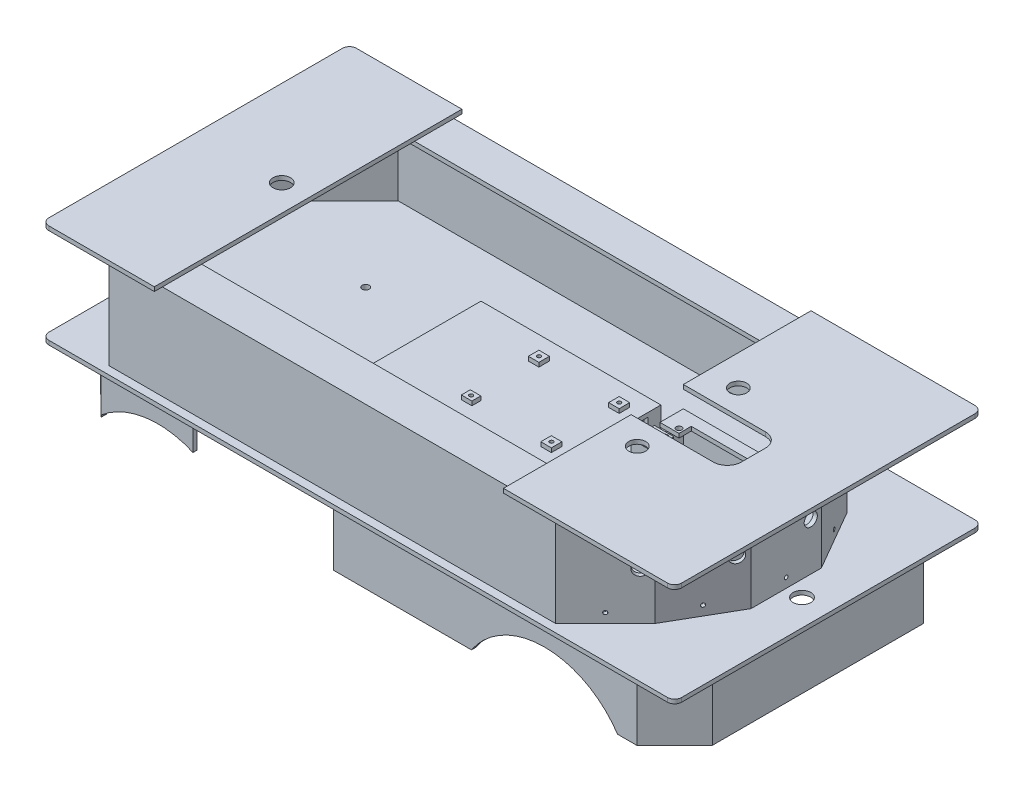
SolidWorks part; units mm, degrees
material "ABS"
ref_plane "Front Plane" through (0, 0, 0) normal (0, 0, 1) x (1, 0, 0)
ref_plane "Top Plane" through (0, 0, 0) normal (0, 1, 0) x (1, 0, 0)
ref_plane "Right Plane" through (0, 0, 0) normal (1, 0, 0) x (0, 0, -1)
sketch "Sketch1" plane through (0, 0, 0) normal (0, 1, 0) x (1, 0, 0)
  line L0 (-303.5027, 0) -> (303.5027, 0) construction
  line L1 (-223.52, -111.125) -> (223.52, -111.125)
  line L2 (-228.6, -106.045) -> (-228.6, 106.045)
  line L3 (-223.52, 111.125) -> (223.52, 111.125)
  line L4 (228.6, -106.045) -> (228.6, 106.045)
  line L5 (-228.6, -111.125) -> (228.6, 111.125) construction
  line L6 (-228.6, 111.125) -> (228.6, -111.125) construction
  line L7 (-303.5027, 36.5125) -> (303.5027, 36.5125) construction
  line L8 (-303.5027, -36.5125) -> (303.5027, -36.5125) construction
  line L9 (127, 111.125) -> (127, -111.125) construction
  line L10 (-142.24, 111.125) -> (-142.24, -111.125) construction
  arc A0 (223.52, 111.125) -> (228.6, 106.045) centre (223.52, 106.045) cw
  arc A1 (223.52, -111.125) -> (228.6, -106.045) centre (223.52, -106.045) ccw
  arc A2 (-223.52, -111.125) -> (-228.6, -106.045) centre (-223.52, -106.045) cw
  arc A3 (-228.6, 106.045) -> (-223.52, 111.125) centre (-223.52, 106.045) cw
  circle A4 centre (127, 36.5125) radius 2.54
  circle A5 centre (127, -36.5125) radius 2.54
  circle A6 centre (-142.24, 36.5125) radius 2.54
  circle A7 centre (-142.24, -36.5125) radius 2.54
  circle A8 centre (209.55, 0) radius 6.35
  point P0 (0, 0)
  point P20 (0, 0)
  point P37 (228.6, 0)
  dimension "D3" = 5.08
  dimension "D7" = 5.08
  dimension "D9" = 12.7
  dimension "D1" = 222.25
  dimension "D2" = 457.2
  dimension "D6" = 269.24
  dimension "D8" = 101.6
  dimension "D10" = 19.05
  dimension "D4" = 36.5125
  dimension "D5" = 36.5125
extrude "mainbaseplate" add sketch "Sketch1" along normal blind 3
sketch "Sketch2" plane through (0, 0, 0) normal (0, -1, 0) x (1, 0, 0)
  circle A0 centre (-142.24, 36.5125) radius 2.54 construction
  circle A1 centre (-142.24, -36.5125) radius 2.54 construction
  circle A2 centre (127, -36.5125) radius 2.54 construction
  circle A3 centre (127, 36.5125) radius 2.54 construction
  circle A4 centre (-142.24, 36.5125) radius 2.54
  circle A5 centre (-142.24, -36.5125) radius 2.54
  circle A6 centre (127, -36.5125) radius 2.54
  circle A7 centre (127, 36.5125) radius 2.54
  circle A8 centre (127, 36.5125) radius 6.096
  circle A9 centre (127, -36.5125) radius 6.096
  circle A10 centre (-142.24, -36.5125) radius 6.096
  circle A11 centre (-142.24, 36.5125) radius 6.096
  dimension "D1" = 12.192
extrude "BaseBoss-Extrude2" add sketch "Sketch2" along normal blind 10.16
sketch "Sketch3" plane through (0, 0, 0) normal (0, -1, 0) x (1, 0, 0)
  line L0 (-228.6, 0) -> (228.6, 0) construction
  line L1 (-228.6, -106.045) -> (-228.6, 106.045) construction
  line L2 (228.6, 106.045) -> (228.6, -106.045) construction
  line L3 (-228.6, 28.4) -> (-73.2, 28.4)
  line L4 (-228.6, -25.4) -> (-76.2, -25.4)
  line L6 (-228.6, 25.4) -> (-76.2, 25.4)
  line L7 (-76.2, -25.4) -> (-76.2, 25.4)
  line L8 (-228.6, -25.4) -> (-76.2, 25.4) construction
  line L9 (-228.6, 25.4) -> (-76.2, -25.4) construction
  line L10 (-73.2, -28.4) -> (-73.2, 28.4)
  line L11 (-228.6, -28.4) -> (-73.2, -28.4)
  line L12 (-228.6, 28.4) -> (-228.6, 25.4)
  line L13 (-228.6, -25.4) -> (-228.6, -28.4)
  point P6 (-152.4, 0)
  dimension "D1" = 50.8
  dimension "D2" = 152.4
  dimension "D3" = 76.2
  dimension "D4" = 3
extrude "Drive BatteryBoss-Extrude1" add sketch "Sketch3" along normal blind 28.575
sketch "Sketch4" plane through (0, -28.575, 0) normal (0, -1, 0) x (1, 0, 0)
  line L1 (-228.6, 28.4) -> (-73.2, 28.4)
  line L2 (-228.6, 28.4) -> (-228.6, -28.4)
  line L3 (-228.6, -28.4) -> (-73.2, -28.4)
  line L4 (-73.2, 28.4) -> (-73.2, -28.4)
extrude "drive Battery CapBoss-Extrude2" add sketch "Sketch4" along normal blind 3
sketch "Sketch5" plane through (0, -31.575, 0) normal (0, -1, 0) x (1, 0, 0)
  line L0 (-98.6, -28.4) -> (-73.2, -3)
  line L1 (-228.6, -28.4) -> (-73.2, -28.4) construction
  line L2 (-73.2, -28.4) -> (-73.2, 28.4) construction
  line L3 (-73.2, -3) -> (-52.1474, -3)
  line L4 (-52.1474, -3) -> (-52.1474, -43.6373)
  line L5 (-52.1474, -43.6373) -> (-98.6, -43.6373)
  line L6 (-98.6, -43.6373) -> (-98.6, -28.4)
  dimension "D1" = 25.4
  dimension "D2" = 25.4
  dimension "D3" = 21.0526
  dimension "D4" = 15.2373
extrude "Drive batterycutoutCut-Extrude1" cut sketch "Sketch5" against normal up to surface (31.575 mm away) up to face at (-142.24, 0, -42.6085)
sketch "Sketch6" plane through (0, 3, 0) normal (0, 1, 0) x (1, 0, 0)
  line L0 (-228.6, 0) -> (228.6, 0) construction
  line L1 (-228.6, 106.045) -> (-228.6, -106.045) construction
  line L2 (228.6, -106.045) -> (228.6, 106.045) construction
  line L3 (-63.5, -41.1) -> (66.5, -41.1)
  line L4 (-63.5, -38.1) -> (63.5, -38.1)
  line L6 (-63.5, 38.1) -> (63.5, 38.1)
  line L7 (63.5, -38.1) -> (63.5, 38.1)
  line L8 (-63.5, -38.1) -> (63.5, 38.1) construction
  line L9 (-63.5, 38.1) -> (63.5, -38.1) construction
  line L10 (66.5, -41.1) -> (66.5, 41.1)
  line L11 (-63.5, 41.1) -> (66.5, 41.1)
  line L12 (-63.5, -41.1) -> (-63.5, -38.1)
  line L13 (-63.5, 38.1) -> (-63.5, 41.1)
  point P6 (0, 0)
  dimension "D1" = 127
  dimension "D2" = 76.2
  dimension "D4" = 63.5
  dimension "D3" = 3
extrude "PiBatteryBoxBoss-Extrude3" add sketch "Sketch6" along normal blind 25.4
sketch "Sketch7" plane through (0, 28.4, 0) normal (0, 1, 0) x (1, 0, 0)
  line L1 (66.5, 41.1) -> (-63.5, 41.1)
  line L2 (66.5, 41.1) -> (66.5, -41.1)
  line L3 (66.5, -41.1) -> (-63.5, -41.1)
  line L4 (-63.5, 41.1) -> (-63.5, -41.1)
extrude "PibatterytopBoss-Extrude4" add sketch "Sketch7" along normal blind 3
sketch "Sketch8" plane through (66.5, 0, 0) normal (1, 0, 0) x (0, 0, -1)
  line L0 (-38.1, 28.4) -> (38.1, 3) construction
  line L1 (38.1, 28.4) -> (-38.1, 28.4) construction
  line L2 (-31.75, 3) -> (31.75, 3)
  line L3 (-31.75, 3) -> (-31.75, 28.4)
  line L4 (-31.75, 28.4) -> (31.75, 28.4)
  line L5 (31.75, 3) -> (31.75, 28.4)
  line L6 (-31.75, 3) -> (31.75, 28.4) construction
  line L7 (-31.75, 28.4) -> (31.75, 3) construction
  point P2 (0, 15.7)
  dimension "D1" = 31.75
extrude "pibatterywiresCut-Extrude2" cut sketch "Sketch8" against normal blind 13.16
sketch "Sketch9" plane through (0, 31.4, 0) normal (0, 1, 0) x (1, 0, 0)
  line L0 (-63.5, 41.1) -> (66.5, -41.1) construction
  line L1 (-63.5, 0) -> (66.5, 0) construction
  line L2 (-5.08, -24.489) -> (52.92, -24.489) construction
  line L3 (-5.08, -24.489) -> (-5.08, 24.511) construction
  line L4 (-5.08, 24.511) -> (52.92, 24.511) construction
  line L5 (52.92, -24.489) -> (52.92, 24.511) construction
  line L6 (-5.08, -24.489) -> (52.92, 24.511) construction
  line L7 (-5.08, 24.511) -> (52.92, -24.489) construction
  line L8 (49.11, 20.701) -> (56.73, 20.701)
  line L9 (49.11, 20.701) -> (49.11, 28.321)
  line L10 (49.11, 28.321) -> (56.73, 28.321)
  line L11 (56.73, 20.701) -> (56.73, 28.321)
  line L12 (49.11, 20.701) -> (56.73, 28.321) construction
  line L13 (49.11, 28.321) -> (56.73, 20.701) construction
  line L14 (49.11, -28.299) -> (56.73, -28.299)
  line L16 (49.11, -20.679) -> (56.73, -20.679)
  line L18 (49.11, -28.299) -> (56.73, -20.679) construction
  line L19 (49.11, -20.679) -> (56.73, -28.299) construction
  line L20 (-8.89, 20.701) -> (-1.27, 20.701)
  line L21 (-8.89, 20.701) -> (-8.89, 28.321)
  line L22 (-8.89, 28.321) -> (-1.27, 28.321)
  line L23 (-1.27, 20.701) -> (-1.27, 28.321)
  line L24 (-8.89, 20.701) -> (-1.27, 28.321) construction
  line L25 (-8.89, 28.321) -> (-1.27, 20.701) construction
  line L26 (-8.89, -27.7078) -> (-1.27, -27.7078)
  line L27 (-8.89, -27.7078) -> (-8.89, -21.2702)
  line L28 (-8.89, -21.2702) -> (-1.27, -21.2702)
  line L29 (-1.27, -27.7078) -> (-1.27, -21.2702)
  line L30 (-8.89, -27.7078) -> (-1.27, -21.2702) construction
  line L31 (-8.89, -21.2702) -> (-1.27, -27.7078) construction
  line L32 (-63.5, 41.1) -> (-63.5, -41.1) construction
  line L33 (66.5, -41.1) -> (66.5, 41.1) construction
  line L34 (56.73, -20.679) -> (56.73, -28.299)
  line L35 (49.11, -20.679) -> (49.11, -28.299)
  circle A0 centre (52.92, 24.511) radius 1.35
  circle A1 centre (-5.08, 24.511) radius 1.35
  circle A2 centre (-5.08, -24.489) radius 1.35
  circle A3 centre (52.92, -24.489) radius 1.35
  point P4 (-8.057, 0)
  dimension "D3" = 2.7
  dimension "D4" = 7.62
  dimension "D1" = 58
  dimension "D2" = 49
  dimension "D5" = 7.62
  dimension "D6" = 7.62
  dimension "D7" = 7.62
  dimension "D8" = 7.62
  dimension "D9" = 7.62
  dimension "D10" = 58.42
  dimension "D11" = 24.511
  dimension "D12" = 7.62
extrude "PiBoardBoss-Extrude5" add sketch "Sketch9" along normal blind 3
sketch "Sketch10" plane through (0, 3, 0) normal (0, 1, 0) x (1, 0, 0)
  line L0 (228.6, 0) -> (-228.6, 0) construction
  line L1 (228.6, -106.045) -> (228.6, 106.045) construction
  line L2 (-228.6, 106.045) -> (-228.6, -106.045) construction
  line L3 (104.95, 18.875) -> (174.45, 18.875)
  line L4 (107.95, -15.875) -> (171.45, -15.875)
  line L5 (107.95, -15.875) -> (107.95, -6.175)
  line L6 (107.95, 15.875) -> (171.45, 15.875)
  line L7 (171.45, -15.875) -> (171.45, 15.875)
  line L8 (107.95, -15.875) -> (171.45, 15.875) construction
  line L9 (107.95, 15.875) -> (171.45, -15.875) construction
  line L10 (174.45, -18.875) -> (174.45, 18.875)
  line L11 (104.95, -18.875) -> (174.45, -18.875)
  line L12 (104.95, -18.875) -> (104.95, -6.175)
  line L13 (104.95, 6.175) -> (107.95, 6.175)
  line L14 (104.95, -6.175) -> (107.95, -6.175)
  line L15 (104.95, 6.175) -> (104.95, 18.875)
  line L16 (104.95, -18.875) -> (104.95, 18.875) construction
  line L17 (107.95, 6.175) -> (107.95, 15.875)
  line L18 (107.95, -15.875) -> (107.95, 15.875) construction
  point P6 (139.7, 0)
  dimension "D1" = 31.75
  dimension "D2" = 63.5
  dimension "D3" = 139.7
  dimension "D5" = 12.7
  dimension "D6" = 12.7
  dimension "D4" = 3
extrude "PanTilt-Extrude6" add sketch "Sketch10" along normal blind 53.34
sketch "Sketch11" plane through (0, 56.34, 0) normal (0, 1, 0) x (1, 0, 0)
  line L1 (104.95, 18.875) -> (174.45, 18.875)
  line L2 (104.95, 18.875) -> (104.95, -18.875)
  line L3 (104.95, -18.875) -> (174.45, -18.875)
  line L4 (174.45, 18.875) -> (174.45, -18.875)
extrude "Boss-Extrude7" add sketch "Sketch11" along normal blind 3
sketch "Sketch12" plane through (0, 59.34, 0) normal (0, 1, 0) x (1, 0, 0)
  line L0 (104.95, 0) -> (174.45, 0) construction
  line L1 (104.95, 18.875) -> (104.95, -18.875) construction
  line L2 (174.45, -18.875) -> (174.45, 18.875) construction
  line L3 (118.745, 1.9377) -> (104.95, 1.9377)
  line L4 (118.745, -10.795) -> (160.655, -10.795)
  line L5 (118.745, -10.795) -> (118.745, -1.9901)
  line L6 (118.745, 10.795) -> (160.655, 10.795)
  line L7 (160.655, -10.795) -> (160.655, 10.795)
  line L8 (118.745, -10.795) -> (160.655, 10.795) construction
  line L9 (118.745, 10.795) -> (160.655, -10.795) construction
  line L10 (115.57, -5.08) -> (163.83, -5.08) construction
  line L11 (115.57, -5.08) -> (115.57, 5.08) construction
  line L12 (115.57, 5.08) -> (163.83, 5.08) construction
  line L13 (163.83, -5.08) -> (163.83, 5.08) construction
  line L14 (115.57, -5.08) -> (163.83, 5.08) construction
  line L15 (115.57, 5.08) -> (163.83, -5.08) construction
  line L16 (118.745, -1.9901) -> (104.95, -1.9901)
  line L17 (118.745, 1.9377) -> (118.745, 10.795)
  line L18 (104.95, 1.9377) -> (95.8416, 0)
  line L19 (95.8416, 0) -> (104.95, -1.9901)
  circle A0 centre (163.83, 5.08) radius 2.0193
  circle A1 centre (163.83, -5.08) radius 2.0193
  circle A2 centre (115.57, 5.08) radius 2.0193
  circle A3 centre (115.57, -5.08) radius 2.0193
  point P6 (139.7, 0)
  point P11 (139.7, 0)
  dimension "D5" = 4.0386
  dimension "D1" = 21.59
  dimension "D2" = 41.91
  dimension "D3" = 48.26
  dimension "D4" = 10.16
  dimension "D6" = 1.9377
  dimension "D7" = 1.9901
extrude "Cut-Extrude3" cut sketch "Sketch12" against normal up to surface (56.34 mm away) up to face at (22.1667, 3, 36.9833)
sketch "Sketch13" plane through (0, 3, 0) normal (0, 1, 0) x (1, 0, 0)
  line L0 (228.6, 0) -> (-228.6, 0) construction
  line L1 (228.6, -106.045) -> (228.6, 106.045) construction
  line L2 (-228.6, 106.045) -> (-228.6, -106.045) construction
  line L3 (198.12, 0) -> (198.12, 25.4)
  line L4 (198.12, 25.4) -> (172.72, 69.3941)
  line L5 (172.72, 69.3941) -> (136.799, 105.3151)
  line L6 (198.12, 25.4) -> (198.12, 129.9736) construction
  line L7 (172.72, 69.3941) -> (172.72, 97.5573) construction
  line L8 (136.799, 105.3151) -> (-185.781, 105.3151)
  line L9 (-185.781, 105.3151) -> (-221.702, 69.3941)
  line L10 (-221.702, 69.3941) -> (-221.702, 0)
  line L11 (-185.781, 105.3151) -> (-290.6809, 105.3151) construction
  line L12 (195.12, 0) -> (195.12, 24.5962)
  line L13 (195.12, 24.5962) -> (170.3194, 67.552)
  line L14 (170.3194, 67.552) -> (135.5563, 102.3151)
  line L15 (135.5563, 102.3151) -> (-184.5384, 102.3151)
  line L16 (-184.5384, 102.3151) -> (-218.702, 68.1514)
  line L17 (-218.702, 68.1514) -> (-218.702, 0)
  line L18 (172.72, -69.3941) -> (172.72, -97.5573) construction
  line L19 (198.12, -25.4) -> (198.12, -129.9736) construction
  line L20 (-218.702, -68.1514) -> (-218.702, 0)
  line L21 (-184.5384, -102.3151) -> (-218.702, -68.1514)
  line L22 (135.5563, -102.3151) -> (-184.5384, -102.3151)
  line L23 (170.3194, -67.552) -> (135.5563, -102.3151)
  line L24 (195.12, -24.5962) -> (170.3194, -67.552)
  line L25 (195.12, 0) -> (195.12, -24.5962)
  line L26 (-221.702, -69.3941) -> (-221.702, 0)
  line L27 (-185.781, -105.3151) -> (-221.702, -69.3941)
  line L28 (136.799, -105.3151) -> (-185.781, -105.3151)
  line L29 (172.72, -69.3941) -> (136.799, -105.3151)
  line L30 (198.12, -25.4) -> (172.72, -69.3941)
  line L31 (198.12, 0) -> (198.12, -25.4)
  dimension "D1" = 30.48
  dimension "D2" = 25.4
  dimension "D3" = 30
  dimension "D4" = 50.8
  dimension "D5" = 45
  dimension "D6" = 50.8
  dimension "D7" = 322.58
  dimension "D8" = 50.8
  dimension "D9" = 45
  dimension "D10" = 3
extrude "Bottom Shell WallsBoss-Extrude8" add sketch "Sketch13" along normal blind 68.58
sketch "Sketch14" plane through (121.057, 0, -121.057) normal (0.7071, 0, -0.7071) x (-0.7071, 0, -0.7071)
  line L0 (-47.6625, 71.58) -> (-47.6625, 3) construction
  line L1 (-73.0625, 71.58) -> (-22.2625, 71.58) construction
  line L2 (-73.0625, 3) -> (-22.2625, 3) construction
  line L3 (-47.6625, 37.29) -> (-25.0131, 37.29) construction
  circle A0 centre (-47.6625, 64.722) radius 1.3526
  circle A1 centre (-47.6625, 9.858) radius 1.3526
  circle A2 centre (-29.8825, 37.29) radius 4.7625
  point P10 (-47.6625, 37.29)
  dimension "D1" = 2.7051
  dimension "D4" = 9.525
  dimension "D2" = 54.864
  dimension "D3" = 27.432
  dimension "D5" = 17.78
extrude "Sharp1Cut-Extrude4" cut sketch "Sketch14" against normal blind 12.7
sketch "Sketch15" plane through (159.5885, 0, -92.1385) normal (0.866, 0, -0.5) x (-0.5, 0, -0.866)
  line L0 (-51.663, 71.58) -> (-51.663, 3) construction
  line L1 (-77.063, 71.58) -> (-26.263, 71.58) construction
  line L2 (-77.063, 3) -> (-26.263, 3) construction
  line L3 (-51.663, 37.29) -> (-29.7061, 37.29) construction
  circle A0 centre (-51.663, 64.722) radius 1.3526
  circle A1 centre (-51.663, 9.858) radius 1.3526
  circle A2 centre (-33.883, 37.29) radius 4.7625
  point P10 (-51.663, 37.29)
  dimension "D1" = 2.7051
  dimension "D4" = 9.525
  dimension "D2" = 27.432
  dimension "D3" = 54.864
  dimension "D5" = 17.78
extrude "Sharp2Cut-Extrude5" cut sketch "Sketch15" against normal blind 7.62
sketch "Sketch16" plane through (198.12, 0, 0) normal (1, 0, 0) x (0, 0, -1)
  line L0 (0, 71.58) -> (0, 3) construction
  line L1 (-25.4, 71.58) -> (25.4, 71.58) construction
  line L2 (-25.4, 3) -> (25.4, 3) construction
  line L3 (0, 37.29) -> (21.2381, 37.29) construction
  circle A0 centre (0, 64.722) radius 1.3526
  circle A1 centre (0, 9.858) radius 1.3525
  circle A2 centre (17.78, 37.29) radius 4.7625
  dimension "D1" = 2.7051
  dimension "D4" = 9.525
  dimension "D2" = 27.432
  dimension "D3" = 54.864
  dimension "D5" = 17.78
extrude "Sharp3Cut-Extrude6" cut sketch "Sketch16" against normal blind 7.62
sketch "Sketch17" plane through (159.5885, 0, 92.1385) normal (0.866, 0, 0.5) x (0.5, 0, -0.866)
  line L0 (51.663, 71.58) -> (51.663, 3) construction
  line L1 (26.263, 71.58) -> (77.063, 71.58) construction
  line L2 (26.263, 3) -> (77.063, 3) construction
  line L3 (51.663, 37.29) -> (70.4023, 37.29) construction
  circle A0 centre (51.663, 64.722) radius 1.3526
  circle A1 centre (51.663, 9.858) radius 1.3526
  circle A2 centre (69.443, 37.29) radius 4.7625
  dimension "D1" = 2.7051
  dimension "D2" = 2.7051
  dimension "D3" = 9.525
  dimension "D4" = 17.78
  dimension "D5" = 27.432
  dimension "D6" = 54.864
extrude "SharpCut-Extrude7" cut sketch "Sketch17" against normal blind 7.62
sketch "Sketch18" plane through (121.057, 0, 121.057) normal (0.7071, 0, 0.7071) x (0.7071, 0, -0.7071)
  line L0 (47.6625, 71.58) -> (47.6625, 3) construction
  line L1 (22.2625, 71.58) -> (73.0625, 71.58) construction
  line L2 (22.2625, 3) -> (73.0625, 3) construction
  line L3 (25.604, 37.29) -> (69.7209, 37.29) construction
  circle A0 centre (47.6625, 64.722) radius 1.3526
  circle A1 centre (47.6625, 9.858) radius 1.3526
  circle A2 centre (65.4425, 37.29) radius 4.7625
  point P13 (47.6625, 37.29)
  dimension "D1" = 9.525
  dimension "D3" = 2.7051
  dimension "D4" = 2.7051
  dimension "D2" = 17.78
  dimension "D5" = 27.432
  dimension "D6" = 54.864
extrude "SharpCut-Extrude8" cut sketch "Sketch18" against normal blind 7.62
sketch "Sketch19" plane through (0, 71.58, 0) normal (0, 1, 0) x (1, 0, 0)
  line L0 (-223.52, -111.125) -> (223.52, -111.125) construction
  line L1 (228.6, -106.045) -> (228.6, 106.045) construction
  line L2 (223.52, 111.125) -> (-223.52, 111.125) construction
  line L3 (104.95, -111.125) -> (223.52, -111.125)
  line L4 (228.6, -106.045) -> (228.6, 106.045)
  line L5 (223.52, 111.125) -> (104.95, 111.125)
  line L6 (104.95, 111.125) -> (104.95, -111.125)
  arc A0 (223.52, -111.125) -> (228.6, -106.045) centre (223.52, -106.045) ccw construction
  arc A1 (228.6, 106.045) -> (223.52, 111.125) centre (223.52, 106.045) ccw construction
  arc A2 (223.52, -111.125) -> (228.6, -106.045) centre (223.52, -106.045) ccw
  arc A3 (228.6, 106.045) -> (223.52, 111.125) centre (223.52, 106.045) ccw
extrude "TopSensorplateBoss-Extrude8" add sketch "Sketch19" along normal blind 3
sketch "Sketch21" plane through (0, 74.58, 0) normal (0, 1, 0) x (1, 0, 0)
  line L0 (104.95, -18.875) -> (174.45, -18.875) construction
  line L1 (174.45, -18.875) -> (174.45, 18.875) construction
  line L2 (174.45, 18.875) -> (104.95, 18.875) construction
  line L3 (104.95, -18.875) -> (164.29, -18.875)
  line L4 (174.45, -8.715) -> (174.45, 8.715)
  line L5 (164.29, 18.875) -> (104.95, 18.875)
  line L6 (104.95, 18.875) -> (84.8462, 2.2825)
  line L7 (84.8462, 2.2825) -> (104.95, -18.875)
  arc A0 (164.29, -18.875) -> (174.45, -8.715) centre (164.29, -8.715) ccw
  arc A1 (174.45, 8.715) -> (164.29, 18.875) centre (164.29, 8.715) ccw
  circle A2 centre (127, -36.5125) radius 6.096 construction
  circle A3 centre (127, 36.5125) radius 6.096 construction
  circle A4 centre (127, -36.5125) radius 6.096
  circle A5 centre (127, 36.5125) radius 6.096
  dimension "D1" = 10.16
extrude "topsensorplateCut-Extrude4" cut sketch "Sketch21" against normal blind 8.08
sketch "Sketch22" plane through (0, 0, 0) normal (0, -1, 0) x (1, 0, 0)
  line L0 (228.6, 0) -> (-228.6, 0) construction
  line L1 (228.6, 106.045) -> (228.6, -106.045) construction
  line L2 (-228.6, 28.4) -> (-228.6, -28.4) construction
  line L3 (220.98, 0) -> (220.98, 76.2)
  line L4 (220.98, 76.2) -> (193.675, 103.505)
  line L5 (193.675, 103.505) -> (-25.4, 103.505)
  line L6 (-223.52, 111.125) -> (223.52, 111.125) construction
  line L7 (217.98, 0) -> (217.98, 74.9574)
  line L8 (217.98, 74.9574) -> (192.4324, 100.505)
  line L9 (192.4324, 100.505) -> (-25.4, 100.505)
  line L10 (-25.4, 103.505) -> (-25.4, 100.505)
  line L11 (217.98, 0) -> (217.98, -74.9574)
  line L12 (220.98, 0) -> (220.98, -76.2)
  line L13 (-25.4, -103.505) -> (-25.4, -100.505)
  line L14 (192.4324, -100.505) -> (-25.4, -100.505)
  line L15 (217.98, -74.9574) -> (192.4324, -100.505)
  line L16 (193.675, -103.505) -> (-25.4, -103.505)
  line L17 (220.98, -76.2) -> (193.675, -103.505)
  line L18 (-220.98, 28.4) -> (-220.98, 76.2)
  line L19 (-73.2, 28.4) -> (-228.6, 28.4) construction
  line L20 (-220.98, 76.2) -> (-193.548, 103.505)
  line L21 (-193.548, 103.505) -> (-127, 103.505)
  line L22 (-228.6, 28.4) -> (-228.6, 106.045) construction
  line L23 (-217.98, 28.4) -> (-217.98, 74.9533)
  line L24 (-217.98, 74.9533) -> (-192.3094, 100.505)
  line L25 (-192.3094, 100.505) -> (-127, 100.505)
  line L26 (-127, 103.505) -> (-127, 100.505)
  line L27 (-220.98, 28.4) -> (-217.98, 28.4)
  line L28 (-127, -103.505) -> (-127, -100.505)
  line L29 (-192.3094, -100.505) -> (-127, -100.505)
  line L30 (-217.98, -74.9533) -> (-192.3094, -100.505)
  line L31 (-217.98, -28.4) -> (-217.98, -74.9533)
  line L32 (-193.548, -103.505) -> (-127, -103.505)
  line L33 (-220.98, -76.2) -> (-193.548, -103.505)
  line L34 (-220.98, -28.4) -> (-220.98, -76.2)
  line L35 (-220.98, -28.4) -> (-217.98, -28.4)
  dimension "D1" = 7.62
  dimension "D2" = 7.62
  dimension "D3" = 76.2
  dimension "D4" = 34.925
  dimension "D5" = 254
  dimension "D7" = 7.62
  dimension "D8" = 76.2
  dimension "D9" = 7.62
  dimension "D10" = 101.6
  dimension "D11" = 35.052
  dimension "D6" = 3
  dimension "D12" = 3
extrude "frontrockerpanBoss-Extrude9" add sketch "Sketch22" along normal blind 45.72
sketch "Sketch23" plane through (0, 0, -103.505) normal (0, 0, -1) x (-1, 0, 0)
  line L0 (25.4, 0) -> (-193.675, 0) construction
  line L2 (-223.1134, -81.0052) -> (22.7571, -81.0052) construction
  line L3 (22.7571, -81.0052) -> (254.0819, -81.0052) construction
  circle A1 centre (-127, -81.0052) radius 63.5
  circle A2 centre (152.4, -81.0052) radius 63.5
  dimension "D1" = 81.0052
  dimension "D4" = 127
  dimension "D2" = 22.7571
  dimension "D3" = 223.1134
  dimension "D5" = 127
  dimension "D6" = 279.4
extrude "TireCut-Extrude5" cut sketch "Sketch23" against normal blind 25.4
sketch "Sketch24" plane through (-221.702, 0, 0) normal (-1, 0, 0) x (0, 0, 1)
  line L0 (-69.3941, 71.58) -> (69.3941, 3) construction
  circle A0 centre (0, 37.29) radius 10.9855
  dimension "D1" = 21.971
extrude "Cut-Extrude6" cut sketch "Sketch24" against normal blind 7.62
sketch "Sketch25" plane through (0, 71.58, 0) normal (0, 1, 0) x (1, 0, 0)
  line L3 (-223.52, -111.125) -> (223.52, -111.125) construction
  line L5 (-228.6, 106.045) -> (-228.6, -106.045) construction
  line L6 (223.52, 111.125) -> (-223.52, 111.125) construction
  line L7 (-223.52, -111.125) -> (-147.32, -111.125)
  line L8 (-228.6, 106.045) -> (-228.6, -106.045)
  line L9 (-147.32, 111.125) -> (-223.52, 111.125)
  line L10 (-147.32, 111.125) -> (-147.32, -111.125)
  arc A2 (-228.6, -106.045) -> (-223.52, -111.125) centre (-223.52, -106.045) ccw construction
  arc A3 (-223.52, 111.125) -> (-228.6, 106.045) centre (-223.52, 106.045) ccw construction
  arc A4 (-228.6, -106.045) -> (-223.52, -111.125) centre (-223.52, -106.045) ccw
  arc A5 (-223.52, 111.125) -> (-228.6, 106.045) centre (-223.52, 106.045) ccw
  dimension "D1" = 147.32
extrude "ReartopdeckBoss-Extrude10" add sketch "Sketch25" along normal blind 3
sketch "Sketch28" plane through (0, 0, 103.505) normal (0, 0, 1) x (1, 0, 0)
  line L0 (-205.194, -45.72) -> (-93.1399, -108.4782)
  line L1 (-93.1399, -108.4782) -> (179.794, -45.72)
  line L2 (74.206, -45.72) -> (-102.0458, -69.7467)
  line L3 (-102.0458, -69.7467) -> (-127, -22.8065)
  arc A0 (-192.3094, -31.6141) -> (-205.194, -45.72) centre (-152.4, -81.0052) ccw construction
  arc A1 (-127, -22.8065) -> (-192.3094, -31.6141) centre (-152.4, -81.0052) ccw construction
  arc A2 (179.794, -45.72) -> (74.206, -45.72) centre (127, -81.0052) ccw construction
  arc A3 (-192.3094, -31.6141) -> (-205.194, -45.72) centre (-152.4, -81.0052) ccw
  arc A4 (-127, -22.8065) -> (-192.3094, -31.6141) centre (-152.4, -81.0052) ccw
  arc A5 (179.794, -45.72) -> (74.206, -45.72) centre (127, -81.0052) ccw
extrude "TireCut-Extrude8" cut sketch "Sketch28" against normal blind 35.56
sketch "Sketch30" plane through (0, 74.58, 0) normal (0, 1, 0) x (1, 0, 0)
  line L0 (-147.32, 0) -> (-228.6, 0) construction
  line L1 (-147.32, -111.125) -> (-147.32, 111.125) construction
  line L2 (-228.6, 106.045) -> (-228.6, -106.045) construction
  circle A0 centre (-166.37, 0) radius 6.35
  dimension "D1" = 12.7
  dimension "D2" = 19.05
extrude "Cut-Extrude10" cut sketch "Sketch30" against normal blind 11.684
sketch "Sketch31" plane through (0, 0, 0) normal (1, 0, 0) x (0, 0, -1)
  line L0 (102.3151, 71.58) -> (102.3151, 3) construction
  line L1 (-102.3151, 71.58) -> (-76.9151, 71.58)
  line L2 (-102.3151, 71.58) -> (-102.3151, 68.58)
  line L3 (-102.3151, 68.58) -> (-76.9151, 68.58)
  line L4 (102.3151, 71.58) -> (102.3151, 68.58)
  line L5 (-76.9151, 71.58) -> (-76.9151, 68.58)
  line L6 (76.9151, 71.58) -> (76.9151, 68.58)
  line L7 (76.9151, 71.58) -> (102.3151, 71.58)
  line L8 (76.9151, 68.58) -> (102.3151, 68.58)
  dimension "D1" = 3
  dimension "D2" = 25.4
  dimension "D3" = 25.4
extrude "Boss-Extrude8" add sketch "Sketch31" along normal blind 134.62 and the other way blind 180.34
